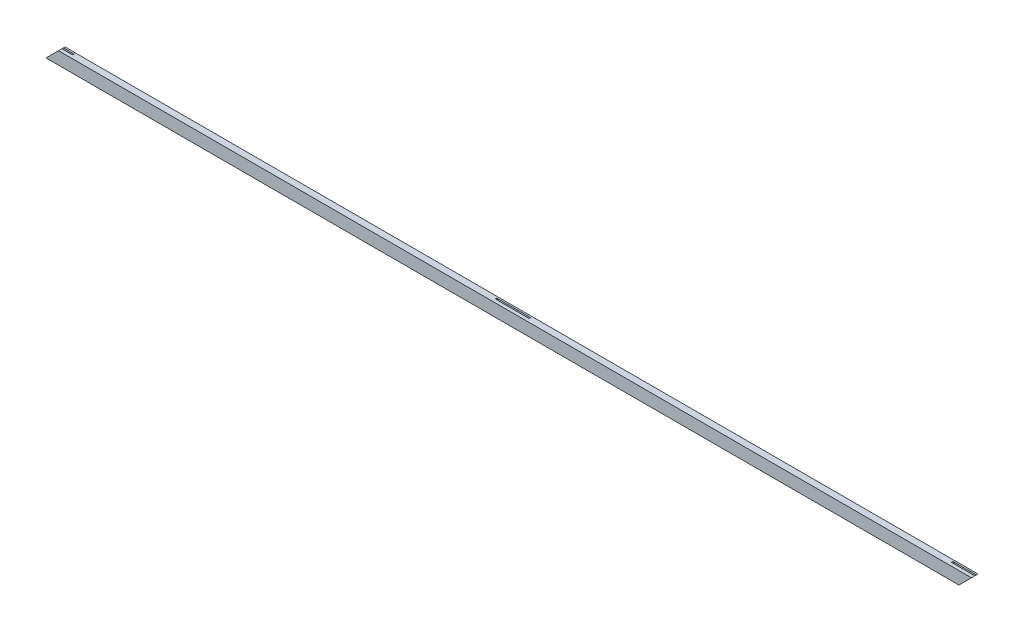
SolidWorks part; units mm, degrees
ref_plane "前视基准面" through (0, 0, 0) normal (0, 0, 1) x (1, 0, 0)
ref_plane "上视基准面" through (0, 0, 0) normal (0, 1, 0) x (1, 0, 0)
ref_plane "右视基准面" through (0, 0, 0) normal (1, 0, 0) x (0, 0, -1)
sketch "草图1" plane through (0, 0, 0) normal (0, 0, 1) x (1, 0, 0)
  line L0 (48, 48) -> (0, 0)
  line L1 (0, 0) -> (3498, 0)
  line L2 (3498, 0) -> (3546, 48)
  line L3 (3546, 48) -> (48, 48)
  dimension "D1" = 3546
  dimension "D2" = 48
  dimension "D3" = 45
  dimension "D4" = 45
extrude "凸台-拉伸1" add sketch "草图1" along normal blind 25
sketch "草图2" plane through (0, 0, 0) normal (0, -1, 0) x (1, 0, 0)
  line L0 (1715.5, 12) -> (1715.5, 6)
  line L1 (1715.5, 6) -> (1830.5, 6)
  line L2 (1830.5, 6) -> (1830.5, 12)
  line L3 (1830.5, 12) -> (1715.5, 12)
  line L4 (48, 0) -> (0, 0) construction
  line L5 (0, 0) -> (3498, 0) construction
  point P0 (1773, 12)
  point P8 (24, 0)
  dimension "D1" = 115
  dimension "D2" = 1749
  dimension "D3" = 6
  dimension "D4" = 6
extrude "切除-拉伸1" cut sketch "草图2" against normal blind 7.5
draft "拔模1" type of draft neutral plane draft angle 45 faces to draft 2 face at (1830.5, 3.75, 9) face at (1715.5, 3.75, 9) neutral plane through (0, 7.5, 0) neutral plane normal (0, -1, 0) parameters "D1"=45
ref_plane "基准面1" through (0, 24, 0) normal (0, 1, 0) x (1, 0, 0)
mirror "镜向1" about plane through (0, 24, 0) normal (0, 1, 0) of face at (1834.25, 3.75, 9) of face at (1773, 7.5, 9) of face at (1773, 3.75, 6) of face at (1711.75, 3.75, 9) of face at (1773, 3.75, 12)
sketch "草图3" plane through (0, 0, 25) normal (0, 0, 1) x (1, 0, 0)
  line L0 (3456.5, 48) -> (3464, 40.5)
  line L1 (3546, 48) -> (48, 48) construction
  line L2 (3464, 40.5) -> (3538.5, 40.5)
  line L3 (3498, 0) -> (3546, 48) construction
  line L4 (3538.5, 40.5) -> (3546, 48)
  line L5 (3546, 48) -> (3456.5, 48)
  line L6 (3456.5, 0) -> (3464, 7.5)
  line L7 (0, 0) -> (3498, 0) construction
  line L8 (3464, 7.5) -> (3505.5, 7.5)
  line L9 (3505.5, 7.5) -> (3498, 0)
  line L10 (3498, 0) -> (3456.5, 0)
  line L11 (48, 48) -> (40.5, 40.5)
  line L12 (48, 48) -> (0, 0) construction
  line L13 (40.5, 40.5) -> (82, 40.5)
  line L14 (82, 40.5) -> (89.5, 48)
  line L15 (89.5, 48) -> (48, 48)
  line L16 (0, 0) -> (7.5, 7.5)
  line L17 (7.5, 7.5) -> (82, 7.5)
  line L18 (82, 7.5) -> (89.5, 0)
  line L19 (89.5, 0) -> (0, 0)
  point P28 (61.25, 40.5)
  point P29 (44.75, 0)
  dimension "D1" = 82
  dimension "D2" = 34
  dimension "D3" = 7.5
  dimension "D4" = 7.5
  dimension "D5" = 45
  dimension "D6" = 7.5
  dimension "D7" = 7.5
  dimension "D8" = 82
  dimension "D9" = 34
  dimension "D10" = 45
  dimension "D11" = 45
extrude "切除-拉伸2" cut sketch "草图3" against normal blind 6 from offset 13 offset against normal yes
